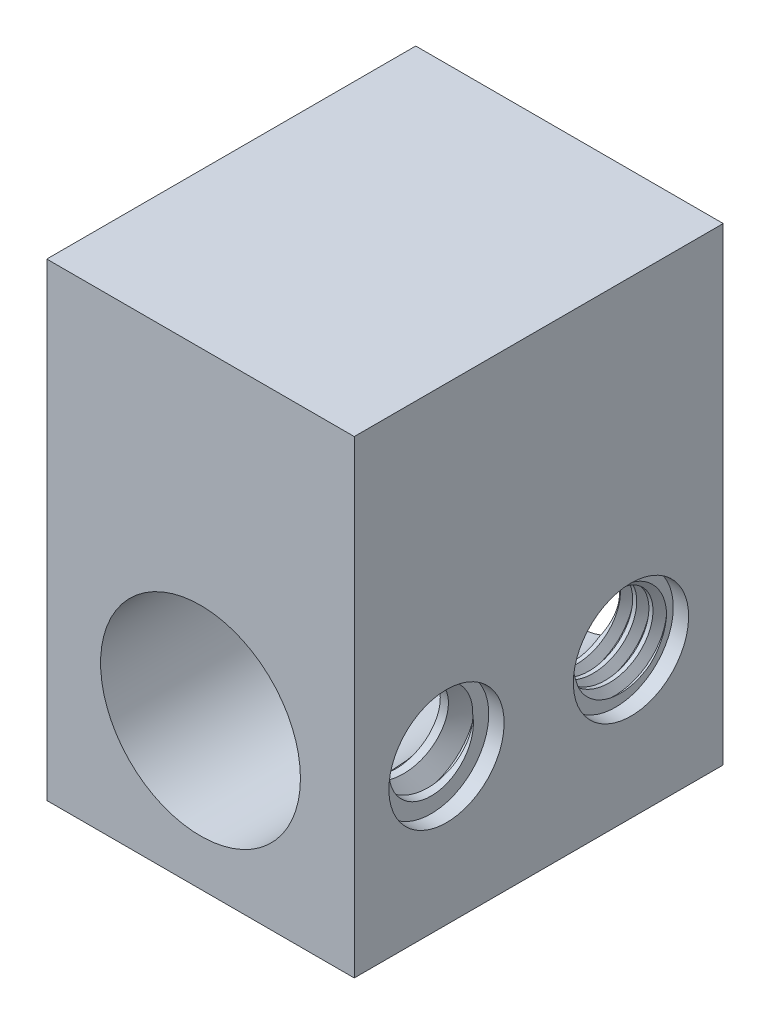
SolidWorks part; units mm, degrees
ref_plane "Front Plane" through (0, 0, 0) normal (0, 0, 1) x (1, 0, 0)
ref_plane "Top Plane" through (0, 0, 0) normal (0, 1, 0) x (1, 0, 0)
ref_plane "Right Plane" through (0, 0, 0) normal (1, 0, 0) x (0, 0, -1)
sketch "Sketch1" plane through (0, 0, 0) normal (0, 0, 1) x (1, 0, 0)
  line L1 (0, 0) -> (-20, 0)
  line L2 (0, 0) -> (0, -30.5)
  line L3 (0, -30.5) -> (-20, -30.5)
  line L4 (-20, 0) -> (-20, -30.5)
  dimension "D1" = 20
  dimension "D2" = 30.5
extrude "Boss-Extrude1" add sketch "Sketch1" along normal blind 24
sketch "Sketch2" plane through (0, 0, 24) normal (0, 0, 1) x (1, 0, 0)
  line L1 (0, 0) -> (-20, 0) construction
  line L2 (-20, -30.5) -> (0, -30.5) construction
  circle A0 centre (-10, -21) radius 6.5
  point P7 (-10, 0)
  dimension "D1" = 9.5
  dimension "D2" = 0
  dimension "D3" = 13
extrude "Cut-Extrude1" cut sketch "Sketch2" against normal blind 40
sketch "Sketch8" plane through (0, 0, 0) normal (0, 0, -1) x (-1, 0, 0)
  line L0 (0, 0) -> (20, 0) construction
  circle A0 centre (10, -10.5) radius 1.75
  point P4 (10, 0)
  dimension "D1" = 0
  dimension "D2" = 3.5
  dimension "D3" = 10.5
extrude "Cut-Extrude5" cut sketch "Sketch8" against normal blind 20
sketch "Sketch13" plane through (0, 0, 0) normal (1, 0, 0) x (0, 0, -1)
  line L0 (-24, -30.5) -> (0, -30.5) construction
  line L1 (0, -30.5) -> (0, 0) construction
  circle A0 centre (-6, -21) radius 2.75
  dimension "D1" = 9.5
  dimension "D2" = 5.5
  dimension "D3" = 6
extrude "Cut-Extrude8" cut sketch "Sketch13" against normal blind 10
thread "Thread3" pitch 1.0583 method cut profile "Thread Profile3" start angle 0, offset 0, length 10, pitch 1.0583, diameter 5.5
ref_plane "Plane3" through (0, -21, 8.75) normal (0, -1, 0) x (0, 0, 1)
sketch "Thread Profile3" plane through (0, -21, 8.75) normal (0, -1, 0) x (0, 0, 1)
  line L0 (0, 0) -> (0, 1.0583) construction
  line L1 (0, 0) -> (0.5728, 0.3307)
  line L2 (0.5728, 0.3307) -> (0.5728, 0.463)
  line L3 (0.5728, 0.463) -> (0, 0.7937)
  line L4 (0.5728, 0.3969) -> (0, 0.3969) construction
  line L11 (0, 0) -> (0, 0.7937)
  point P2 (0, 0)
  dimension "Pitch" = 1.0583
  dimension "Profile_Angle" = 60
  dimension "Profile_Land" = 0.1323
  dimension "Profile_Height" = 0.5728
sketch "Sketch16" plane through (0, 0, 0) normal (1, 0, 0) x (0, 0, -1)
  circle A0 centre (-6, -21) radius 3.75
  dimension "D1" = 7.5
extrude "Cut-Extrude9" cut sketch "Sketch16" against normal blind 1
sketch "Sketch19" plane through (0, 0, 0) normal (1, 0, 0) x (0, 0, -1)
  line L0 (-24, -30.5) -> (-24, 0) construction
  circle A0 centre (-18, -21) radius 2.75
  circle A2 centre (-6, -21) radius 3.75 construction
  dimension "D1" = 6
  dimension "D2" = 5.5
  dimension "D3" = 0
extrude "Cut-Extrude11" cut sketch "Sketch19" against normal blind 10
thread "Thread4" pitch 2.1167 method cut profile "Thread Profile4" start angle 0, offset 0, length 10, pitch 2.1167, diameter 5.5
ref_plane "Plane4" through (0, -21, 20.75) normal (0, -1, 0) x (0, 0, 1)
sketch "Thread Profile4" plane through (0, -21, 20.75) normal (0, -1, 0) x (0, 0, 1)
  line L0 (0, 0) -> (0, 2.1167) construction
  line L1 (0, 0) -> (1.1457, 0.6615)
  line L2 (1.1457, 0.6615) -> (1.1457, 0.926)
  line L3 (1.1457, 0.926) -> (0, 1.5875)
  line L4 (1.1457, 0.7937) -> (0, 0.7937) construction
  line L11 (0, 0) -> (0, 1.5875)
  point P2 (0, 0)
  dimension "Pitch" = 2.1167
  dimension "Profile_Angle" = 60
  dimension "Profile_Land" = 0.2646
  dimension "Profile_Height" = 1.1457
sketch "Sketch22" plane through (0, 0, 0) normal (1, 0, 0) x (0, 0, -1)
  circle A0 centre (-18, -21) radius 3.75
  dimension "D1" = 7.5
extrude "Cut-Extrude12" cut sketch "Sketch22" against normal blind 1
sketch "Sketch23" plane through (0, 0, 0) normal (0, 0, -1) x (-1, 0, 0)
  line L0 (0, -30.5) -> (0, 0) construction
  line L1 (5, -4) -> (2, -4)
  line L2 (5, -4) -> (5, -10)
  line L3 (5, -10) -> (2, -10)
  line L4 (2, -4) -> (2, -10)
  line L5 (0, 0) -> (20, 0) construction
  dimension "D1" = 2
  dimension "D2" = 3
  dimension "D3" = 6
  dimension "D4" = 4
extrude "Cut-Extrude13" cut sketch "Sketch23" against normal blind 14
